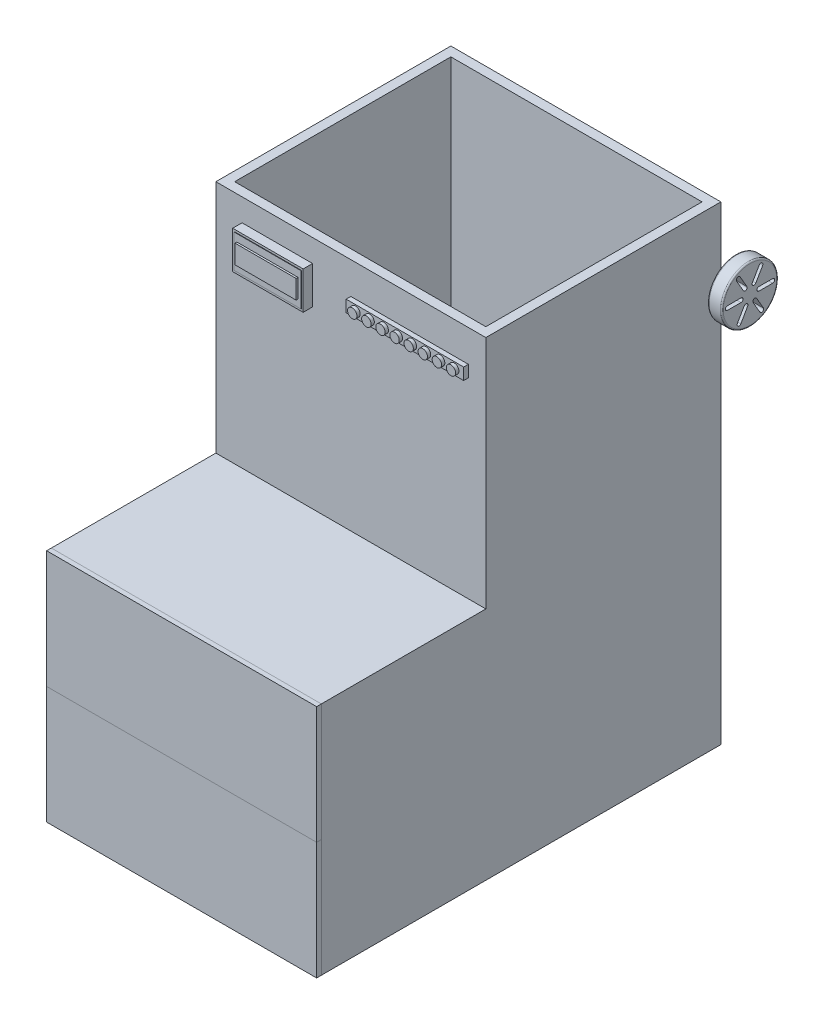
SolidWorks part; units mm, degrees
ref_plane "Front Plane" through (0, 0, 0) normal (1, 0, 0) x (0, 1, 0)
ref_plane "Top Plane" through (0, 0, 0) normal (0, 0, 1) x (0, 1, 0)
ref_plane "Right Plane" through (0, 0, 0) normal (0, 1, 0) x (-1, 0, 0)
sketch "Sketch1" plane through (0, 0, 0) normal (0, 0, 1) x (0, 1, 0)
  line L0 (-50, -28.72) -> (50, -28.72)
  line L1 (-50, -28.72) -> (-50, 28.72)
  line L2 (50, -28.72) -> (50, 28.72)
  line L3 (-50, 28.72) -> (50, 28.72)
  point P1 (0, 0)
extrude "Boss-Extrude1" add sketch "Sketch1" along normal blind 50
shell "Shell1" thickness 2 removed face at (0, 50, 25)
sketch "Sketch2" plane through (0, 0, 50) normal (0, 0, 1) x (1, 0, 0)
  line L0 (-28.72, 50) -> (-28.72, -50) construction
  line L1 (28.72, -50) -> (-28.72, -50)
  line L2 (28.72, -50) -> (28.72, 0)
  line L3 (28.72, 0) -> (-28.72, 0)
  line L4 (-28.72, -50) -> (-28.72, 0)
extrude "Boss-Extrude2" add sketch "Sketch2" along normal blind 35
shell "Shell2" thickness 2 removed face at (0, -25, 85)
sketch "Sketch4" plane through (0, 0, 85) normal (0, 0, 1) x (1, 0, 0)
  line L0 (28.72, -50) -> (28.72, 0) construction
  line L1 (-28.72, 0) -> (28.72, 0)
  line L2 (-28.72, 0) -> (-28.72, -25)
  line L3 (-28.72, -25) -> (28.72, -25)
  line L4 (28.72, 0) -> (28.72, -25)
extrude "Boss-Extrude3" add sketch "Sketch4" along normal blind 1 separate body
sketch "Sketch5" plane through (0, 0, 85) normal (0, 0, 1) x (1, 0, 0)
  line L0 (-28.72, 0) -> (-28.72, -50) construction
  line L1 (-28.72, -25) -> (28.72, -25)
  line L2 (-28.72, -25) -> (-28.72, -50)
  line L3 (-28.72, -50) -> (28.72, -50)
  line L4 (28.72, -25) -> (28.72, -50)
  line L5 (-28.72, -50) -> (28.72, -50) construction
extrude "Boss-Extrude4" add sketch "Sketch5" along normal blind 1 separate body
sketch "Sketch6" plane through (0, 0, 50) normal (0, 0, 1) x (1, 0, 0)
  line L1 (-23.1445, 45.2151) -> (-8.1445, 45.2151)
  line L2 (-23.1445, 45.2151) -> (-23.1445, 37.2151)
  line L3 (-23.1445, 37.2151) -> (-8.1445, 37.2151)
  line L4 (-8.1445, 45.2151) -> (-8.1445, 37.2151)
extrude "Boss-Extrude5" add sketch "Sketch6" along normal blind 2 separate body
sketch "Sketch7" plane through (0, 0, 52) normal (0, 0, 1) x (1, 0, 0)
  line L0 (-8.1445, 37.2151) -> (-8.1445, 45.2151) construction
  line L1 (-22.1445, 43.2151) -> (-9.1445, 43.2151)
  line L2 (-22.1445, 43.2151) -> (-22.1445, 39.2151)
  line L3 (-22.1445, 39.2151) -> (-9.1445, 39.2151)
  line L4 (-9.1445, 43.2151) -> (-9.1445, 39.2151)
  line L5 (-23.1445, 45.2151) -> (-23.1445, 37.2151) construction
  line L6 (-23.1445, 37.2151) -> (-8.1445, 37.2151) construction
  line L7 (-8.1445, 45.2151) -> (-23.1445, 45.2151) construction
  dimension "D1" = 1
  dimension "D2" = 1
  dimension "D3" = 2
  dimension "D4" = 2
extrude "Boss-Extrude6" add sketch "Sketch7" along normal blind 0.5 separate body
sketch "Sketch8" plane through (0, 0, 50) normal (0, 0, 1) x (1, 0, 0)
  line L1 (0, 43.2151) -> (25, 43.2151)
  line L2 (0, 43.2151) -> (0, 40.7151)
  line L3 (0, 40.7151) -> (25, 40.7151)
  line L4 (25, 43.2151) -> (25, 40.7151)
extrude "Boss-Extrude7" add sketch "Sketch8" along normal blind 1 separate body contours L3 L4 L1 L2
sketch "Sketch10" plane through (0, 0, 51) normal (0, 0, 1) x (1, 0, 0)
  line L0 (0, 43.2151) -> (0, 40.7151) construction
  line L2 (0, 43.2151) -> (25, 43.2151) construction
  circle A1 centre (2, 41.9651) radius 1
  dimension "D1" = 2
  dimension "D2" = 1.25
ref_plane "Plane1" through (0, 43.2151, 51) normal (1, 0, 0) x (0, 1, 0)
extrude "Boss-Extrude8" add sketch "Sketch10" along normal blind 0.7 contours A1
pattern_linear "LPattern1" count 8 spacing 3 along (1, 0, 0) of "Boss-Extrude8"
sketch "Sketch14" plane through (28.72, 0, 0) normal (1, 0, 0) x (0, 1, 0)
  line L0 (-50, 0) -> (50, 0) construction
  line L1 (36.0308, 0) -> (31.0308, 0)
  line L2 (36.0308, 0) -> (36.0308, -5)
  line L3 (36.0308, -5) -> (31.0308, -5)
  line L4 (31.0308, 0) -> (31.0308, -5)
extrude "Boss-Extrude9" add sketch "Sketch14" against normal blind 0.7 separate body
sketch "Sketch15" plane through (-28.72, 0, 0) normal (-1, 0, 0) x (0, -1, 0)
  line L0 (-50, 0) -> (50, 0) construction
  line L1 (-36.0308, -5) -> (-31.0308, -5)
  line L2 (-36.0308, -5) -> (-36.0308, 0)
  line L3 (-36.0308, 0) -> (-31.0308, 0)
  line L4 (-31.0308, -5) -> (-31.0308, 0)
  line L5 (-31.0308, 0) -> (-31.0308, -5) construction
extrude "Boss-Extrude10" add sketch "Sketch15" against normal blind 0.7
sketch "Sketch16" plane through (-28.72, 0, 0) normal (-1, 0, 0) x (0, -1, 0)
  line L0 (-36.0308, 0) -> (-36.0308, -5) construction
  line L1 (-36.0308, -5) -> (-31.0308, -5) construction
  circle A0 centre (-33.5308, -2.5) radius 0.5
  dimension "D1" = 2.5
  dimension "D2" = 2.5
extrude "Boss-Extrude11" add sketch "Sketch16" along normal blind 0.7
sketch "Sketch17" plane through (-29.42, 0, 0) normal (-1, 0, 0) x (0, -1, 0)
  line L0 (-33.5308, 2.8254) -> (-33.5308, -1.1746) construction
  circle A0 centre (-33.5308, -2.5) radius 6
  point P7 (-33.5308, 0.8254)
extrude "Boss-Extrude12" add sketch "Sketch17" along normal blind 3
sketch "Sketch18" plane through (-32.42, 0, 0) normal (-1, 0, 0) x (0, -1, 0)
  line L0 (-33.4339, 2.3146) -> (-33.4339, -0.5871) construction
  line L1 (-33.0092, 2.3146) -> (-33.0092, -0.5871)
  line L2 (-33.8585, 2.3146) -> (-33.8585, -0.5871)
  line L3 (-29.5251, 0.1911) -> (-32.0381, -1.2597)
  line L4 (-29.1005, -0.5444) -> (-31.6134, -1.9953)
  line L5 (-29.3128, -0.1767) -> (-31.8257, -1.6275) construction
  line L6 (-29.1974, -4.6235) -> (-31.7104, -3.1726)
  line L7 (-29.6221, -5.359) -> (-32.135, -3.9082)
  line L8 (-29.4098, -4.9912) -> (-31.9227, -3.5404) construction
  line L9 (-33.2031, -7.3146) -> (-33.2031, -4.4129)
  line L10 (-34.0524, -7.3146) -> (-34.0524, -4.4129)
  line L11 (-33.6278, -7.3146) -> (-33.6278, -4.4129) construction
  line L12 (-37.5365, -5.1911) -> (-35.0236, -3.7403)
  line L13 (-37.9612, -4.4556) -> (-35.4483, -3.0047)
  line L14 (-37.7489, -4.8233) -> (-35.2359, -3.3725) construction
  line L15 (-37.8642, -0.3765) -> (-35.3513, -1.8274)
  line L16 (-37.4396, 0.359) -> (-34.9267, -1.0918)
  line L17 (-37.6519, -0.0088) -> (-35.139, -1.4596) construction
  arc A0 (-33.0092, 2.3146) -> (-33.8585, 2.3146) centre (-33.4339, 2.3146) ccw
  arc A1 (-33.8585, -0.5871) -> (-33.0092, -0.5871) centre (-33.4339, -0.5871) ccw
  arc A2 (-29.1005, -0.5444) -> (-29.5251, 0.1911) centre (-29.3128, -0.1767) ccw
  arc A3 (-32.0381, -1.2597) -> (-31.6134, -1.9953) centre (-31.8257, -1.6275) ccw
  arc A4 (-29.6221, -5.359) -> (-29.1974, -4.6235) centre (-29.4098, -4.9912) ccw
  arc A5 (-31.7104, -3.1726) -> (-32.135, -3.9082) centre (-31.9227, -3.5404) ccw
  arc A6 (-34.0524, -7.3146) -> (-33.2031, -7.3146) centre (-33.6278, -7.3146) ccw
  arc A7 (-33.2031, -4.4129) -> (-34.0524, -4.4129) centre (-33.6278, -4.4129) ccw
  arc A8 (-37.9612, -4.4556) -> (-37.5365, -5.1911) centre (-37.7489, -4.8233) ccw
  arc A9 (-35.0236, -3.7403) -> (-35.4483, -3.0047) centre (-35.2359, -3.3725) ccw
  arc A10 (-37.4396, 0.359) -> (-37.8642, -0.3765) centre (-37.6519, -0.0088) ccw
  arc A11 (-35.3513, -1.8274) -> (-34.9267, -1.0918) centre (-35.139, -1.4596) ccw
  circle A12 centre (-33.5308, -2.5) radius 6 construction
  point P2 (-33.4339, 0.8637)
  point P11 (-30.5693, -0.9021)
  point P18 (-30.6662, -4.2658)
  point P25 (-33.6278, -5.8637)
  point P32 (-36.4924, -4.0979)
  point P39 (-36.3955, -0.7342)
  point P44 (-33.5308, -2.5)
extrude "Cut-Extrude2" cut sketch "Sketch18" against normal blind 3
mirror "Mirror6" about plane through (0, 0, 0) normal (1, 0, 0) of "Boss-Extrude10", "Boss-Extrude11", "Boss-Extrude12", "Cut-Extrude2"
fillet "Fillet2" radius 0.3 2 edges at (29.42, 33.5308, 3.5) (32.42, 33.5308, 3.5)
fillet "Fillet3" radius 0.3 2 edges at (-29.42, 33.5308, 3.5) (-32.42, 33.5308, 3.5)
sketch "Sketch21" plane through (0, 0, 52) normal (0, 0, 1) x (1, 0, 0)
  line L1 (-22.7668, 44.7663) -> (-8.4847, 44.7663)
  line L2 (-22.7668, 44.7663) -> (-22.7668, 37.7055)
  line L3 (-22.7668, 37.7055) -> (-8.4847, 37.7055)
  line L4 (-8.4847, 44.7663) -> (-8.4847, 37.7055)
extrude "Boss-Extrude14" add sketch "Sketch21" along normal blind 0.1
sketch "Sketch22" plane through (0, 0, 0) normal (0, 0, -1) x (1, 0, 0)
  circle A0 centre (0, 36.3438) radius 5
extrude "Boss-Extrude15" add sketch "Sketch22" along normal blind 1
fillet "Fillet4" radius 0.3 2 edges at (-5, -36.3438, 0) (-5, -36.3438, -1)
sketch "Sketch23" plane through (0, -50, 0) normal (0, -1, 0) x (1, 0, 0)
  circle A0 centre (-2.5, 4.5414) radius 1.25
  circle A1 centre (2.5, 4.5414) radius 1.25
  dimension "D1" = 2.5
  dimension "D2" = 2.5
  dimension "D3" = 5
  dimension "D4" = 2.5
extrude "Boss-Extrude16" add sketch "Sketch23" along normal blind 0.5 separate body
sketch "Sketch24" plane through (0, -50, 0) normal (0, -1, 0) x (1, 0, 0)
  line L0 (-28.72, 0) -> (28.72, 0) construction
  line L1 (-26.7338, 0) -> (-24.9622, 0)
  line L2 (-26.7338, 0) -> (-26.7338, -2.7442)
  line L3 (-26.7338, -2.7442) -> (-24.9622, -2.7442)
  line L4 (-24.9622, 0) -> (-24.9622, -2.7442)
extrude "Boss-Extrude17" add sketch "Sketch24" against normal blind 1
sketch "Sketch25" plane through (0, 0, -2.7442) normal (0, 0, -1) x (1, 0, 0)
  circle A0 centre (-26.2861, 49.4775) radius 0.375
  circle A1 centre (-25.4109, 49.4775) radius 0.375
  point P4 (-25.4215, 49.6056)
  point P5 (-26.2861, 49.4775)
  point P6 (-25.4109, 49.4775)
  dimension "D1" = 0.75
  dimension "D2" = 0.75
extrude "Boss-Extrude18" add sketch "Sketch25" along normal blind 1
sketch "Sketch26" plane through (0, 0, -1) normal (0, 0, -1) x (0, 1, 0)
  circle A0 centre (-36.6306, 0) radius 3.1297
extrude "Boss-Extrude19" add sketch "Sketch26" along normal blind 8.5
fillet "Fillet5" radius 2 2 edges at (-3.1297, -36.6306, -1) (-3.1297, -36.6306, -9.5)
